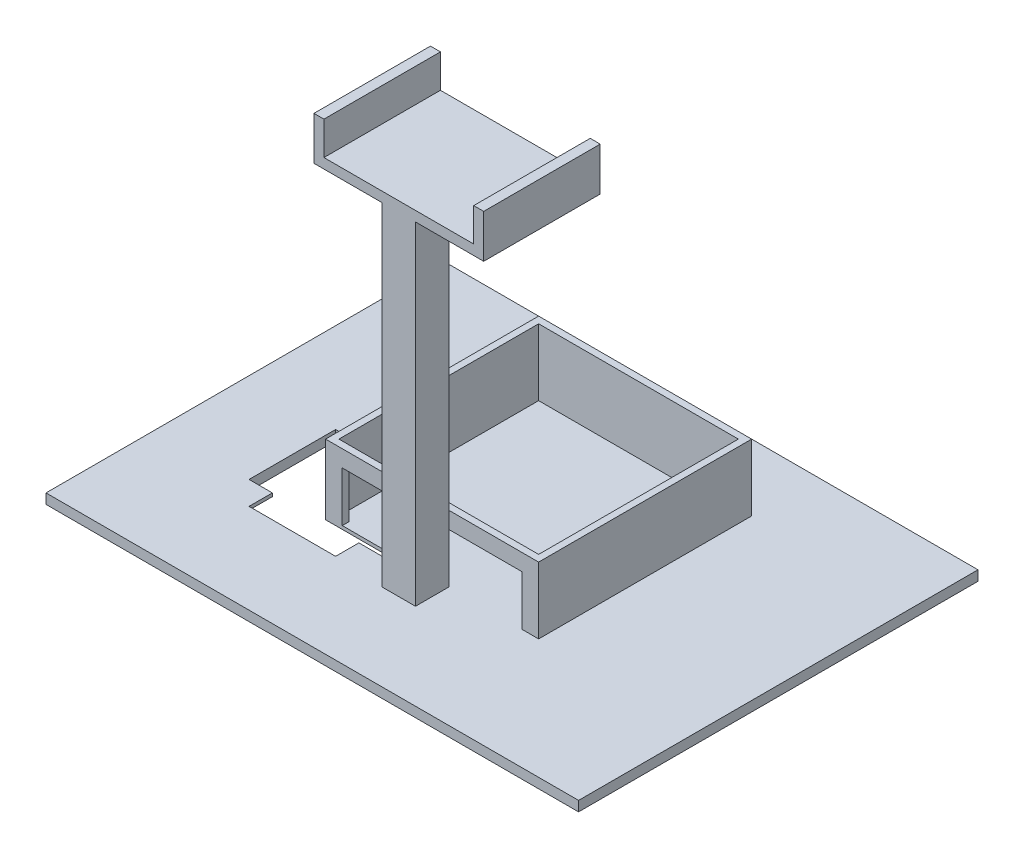
SolidWorks part; units mm, degrees
ref_plane "Front Plane" through (0, 0, 0) normal (0, 0, 1) x (1, 0, 0)
ref_plane "Top Plane" through (0, 0, 0) normal (0, 1, 0) x (1, 0, 0)
ref_plane "Right Plane" through (0, 0, 0) normal (1, 0, 0) x (0, 0, -1)
sketch "Sketch1" plane through (0, 0, 0) normal (0, 1, 0) x (1, 0, 0)
  line L1 (-80, -60) -> (80, -60)
  line L2 (-80, -60) -> (-80, 60)
  line L3 (-80, 60) -> (80, 60)
  line L4 (80, -60) -> (80, 60)
  line L5 (-80, -60) -> (80, 60) construction
  line L6 (-80, 60) -> (80, -60) construction
  point P0 (0, 0)
  dimension "D1" = 160
  dimension "D2" = 120
extrude "Boss-Extrude1" add sketch "Sketch1" along normal blind 3
sketch "Sketch2" plane through (0, 0, 0) normal (0, -1, 0) x (1, 0, 0)
  line L0 (0, 60) -> (0, 50) construction
  line L1 (-80, 60) -> (80, 60) construction
  line L2 (80, 60) -> (80, 50) construction
  line L3 (80, 60) -> (80, -60) construction
  line L4 (80, 50) -> (70, 50) construction
  line L5 (-80, 60) -> (-80, 50) construction
  line L6 (-80, -60) -> (-80, 60) construction
  line L7 (-80, 50) -> (-70, 50) construction
  line L8 (-80, 0) -> (-70, 0) construction
  line L9 (-80, -60) -> (-70, -60) construction
  line L10 (80, -60) -> (-80, -60) construction
  line L11 (-70, -60) -> (-70, -50) construction
  line L12 (80, 0) -> (70, 0) construction
  line L13 (80, -60) -> (70, -60) construction
  line L14 (70, -60) -> (70, -50) construction
  line L15 (0, -60) -> (0, -50) construction
  circle A0 centre (-70, 50) radius 5
  circle A1 centre (0, 50) radius 5
  circle A2 centre (70, 50) radius 5
  circle A3 centre (-70, 0) radius 5
  circle A4 centre (70, 0) radius 5
  circle A5 centre (-70, -50) radius 5
  circle A6 centre (0, -50) radius 5
  circle A7 centre (70, -50) radius 5
  dimension "D12" = 10
  dimension "D13" = 10
  dimension "D14" = 10
  dimension "D15" = 10
  dimension "D16" = 10
  dimension "D17" = 10
  dimension "D18" = 10
  dimension "D19" = 10
  dimension "D20" = 10
  dimension "D1" = 10
  dimension "D2" = 10
  dimension "D3" = 10
  dimension "D4" = 10
  dimension "D5" = 10
  dimension "D6" = 10
  dimension "D7" = 10
  dimension "D8" = 10
  dimension "D9" = 10
  dimension "D10" = 10
  dimension "D11" = 10
extrude "Cut-Extrude1" cut sketch "Sketch2" against normal blind 2
sketch "Sketch3" plane through (0, 0, 0) normal (0, -1, 0) x (1, 0, 0)
  line L0 (-80, 60) -> (-53, 60) construction
  line L1 (-80, 60) -> (80, 60) construction
  line L2 (-53, 60) -> (-53, 33) construction
  line L4 (-53, 33) -> (-13, 33)
  line L5 (-53, 33) -> (-53, -7)
  line L6 (-53, -7) -> (-13, -7)
  line L7 (-13, 33) -> (-13, -7)
  dimension "D1" = 27
  dimension "D2" = 27
  dimension "D3" = 40
  dimension "D4" = 40
extrude "Cut-Extrude2" cut sketch "Sketch3" against normal blind 2
sketch "Sketch4" plane through (0, 2, 0) normal (0, -1, 0) x (1, 0, 0)
  line L0 (-46, 33) -> (-20, 33)
  line L1 (-13, 33) -> (-53, 33) construction
  line L2 (-13, 33) -> (-53, 33) construction
  line L3 (-20, 33) -> (-20, 26)
  line L4 (-20, 26) -> (-13, 26)
  line L5 (-13, -7) -> (-13, 33) construction
  line L6 (-13, 26) -> (-13, 0)
  line L7 (-13, -7) -> (-13, 33) construction
  line L8 (-13, 0) -> (-20, 0)
  line L9 (-20, 0) -> (-20, -7)
  line L10 (-53, -7) -> (-13, -7) construction
  line L11 (-20, -7) -> (-46, -7)
  line L12 (-53, -7) -> (-13, -7) construction
  line L13 (-46, -7) -> (-46, 0)
  line L14 (-46, 0) -> (-53, 0)
  line L15 (-53, 33) -> (-53, -7) construction
  line L16 (-53, 0) -> (-53, 26)
  line L17 (-53, 33) -> (-53, -7) construction
  line L18 (-53, 26) -> (-46, 26)
  line L19 (-46, 26) -> (-46, 33)
  dimension "D1" = 7
  dimension "D2" = 7
  dimension "D3" = 7
  dimension "D4" = 7
  dimension "D5" = 7
  dimension "D6" = 7
  dimension "D7" = 7
  dimension "D8" = 7
extrude "Cut-Extrude3" cut sketch "Sketch4" against normal blind 1
sketch "Sketch5" plane through (0, 3, 0) normal (0, 1, 0) x (1, 0, 0)
  line L0 (0, 60) -> (0, 40) construction
  line L1 (80, 60) -> (-80, 60) construction
  line L2 (0, 40) -> (-32, 40)
  line L3 (-32, 40) -> (-32, -24)
  line L4 (-32, -24) -> (32, -24)
  line L5 (32, -24) -> (32, 40)
  line L6 (32, 40) -> (0, 40)
  dimension "D1" = 32
  dimension "D2" = 32
  dimension "D3" = 64
  dimension "D4" = 20
extrude "Boss-Extrude2" add sketch "Sketch5" along normal blind 20
sketch "Sketch6" plane through (0, 3, 0) normal (0, -1, 0) x (1, 0, 0)
  line L0 (-32, 24) -> (-13, 24)
  line L1 (-13, 24) -> (-13, 0)
  line L2 (-13, 0) -> (-20, 0)
  line L3 (-20, 0) -> (-20, -7)
  line L4 (-20, -7) -> (-32, -7)
  line L5 (-32, -7) -> (-32, 24)
extrude "Boss-Extrude3" add sketch "Sketch6" along normal blind 1
sketch "Sketch7" plane through (0, 23, 0) normal (0, 1, 0) x (1, 0, 0)
  line L0 (32, 40) -> (-32, 40) construction
  line L1 (-30, 38) -> (30, 38)
  line L2 (-30, 38) -> (-30, -22)
  line L3 (-30, -22) -> (30, -22)
  line L4 (30, 38) -> (30, -22)
  line L5 (32, -24) -> (32, 40) construction
  dimension "D1" = 2
  dimension "D2" = 2
  dimension "D3" = 60
  dimension "D4" = 60
extrude "Cut-Extrude4" cut sketch "Sketch7" against normal blind 20
sketch "Sketch8" plane through (0, 0, 24) normal (0, 0, 1) x (1, 0, 0)
  line L0 (-80, 3) -> (80, 3) construction
  line L1 (-27, 3) -> (27, 3)
  line L2 (-27, 3) -> (-27, 18)
  line L3 (-27, 18) -> (27, 18)
  line L4 (27, 3) -> (27, 18)
  line L5 (32, 23) -> (32, 3) construction
  line L6 (-32, 23) -> (-32, 2) construction
  dimension "D1" = 15
  dimension "D2" = 5
  dimension "D3" = 5
extrude "Cut-Extrude5" cut sketch "Sketch8" against normal up to next
sketch "Sketch9" plane through (0, 3, 0) normal (0, 1, 0) x (1, 0, 0)
  line L0 (-27, -24) -> (27, -24) construction
  line L1 (0, -24) -> (5, -24)
  line L2 (5, -24) -> (5, -34)
  line L3 (5, -34) -> (-5, -34)
  line L4 (-5, -24) -> (0, -24)
  line L5 (-5, -24) -> (-5, -34)
  dimension "D1" = 10
  dimension "D2" = 10
  dimension "D3" = 5
extrude "Boss-Extrude4" add sketch "Sketch9" along normal blind 100 contours L3 L5 L4 L1 L2
sketch "Sketch10" plane through (0, 103, 0) normal (0, 1, 0) x (1, 0, 0)
  line L0 (0, -34) -> (25.5, -34)
  line L1 (5, -34) -> (-5, -34) construction
  line L2 (25.5, -34) -> (25.5, 1)
  line L3 (25.5, 1) -> (-25.5, 1)
  line L4 (-25.5, 1) -> (-25.5, -34)
  line L5 (-25.5, -34) -> (0, -34)
  dimension "D1" = 35
  dimension "D2" = 25.5
  dimension "D3" = 51
extrude "Boss-Extrude5" add sketch "Sketch10" along normal blind 3
sketch "Sketch11" plane through (0, 106, 0) normal (0, 1, 0) x (1, 0, 0)
  line L0 (25.5, 1) -> (-25.5, 1) construction
  line L1 (25.5, -34) -> (22.5, -34)
  line L2 (25.5, -34) -> (25.5, 1)
  line L3 (25.5, 1) -> (22.5, 1)
  line L4 (22.5, -34) -> (22.5, 1)
  line L6 (-25.5, -34) -> (-22.5, -34)
  line L7 (-25.5, -34) -> (-25.5, 1)
  line L8 (-25.5, 1) -> (-22.5, 1)
  line L9 (-22.5, -34) -> (-22.5, 1)
  dimension "D1" = 3
  dimension "D2" = 3
extrude "Boss-Extrude6" add sketch "Sketch11" along normal blind 10
